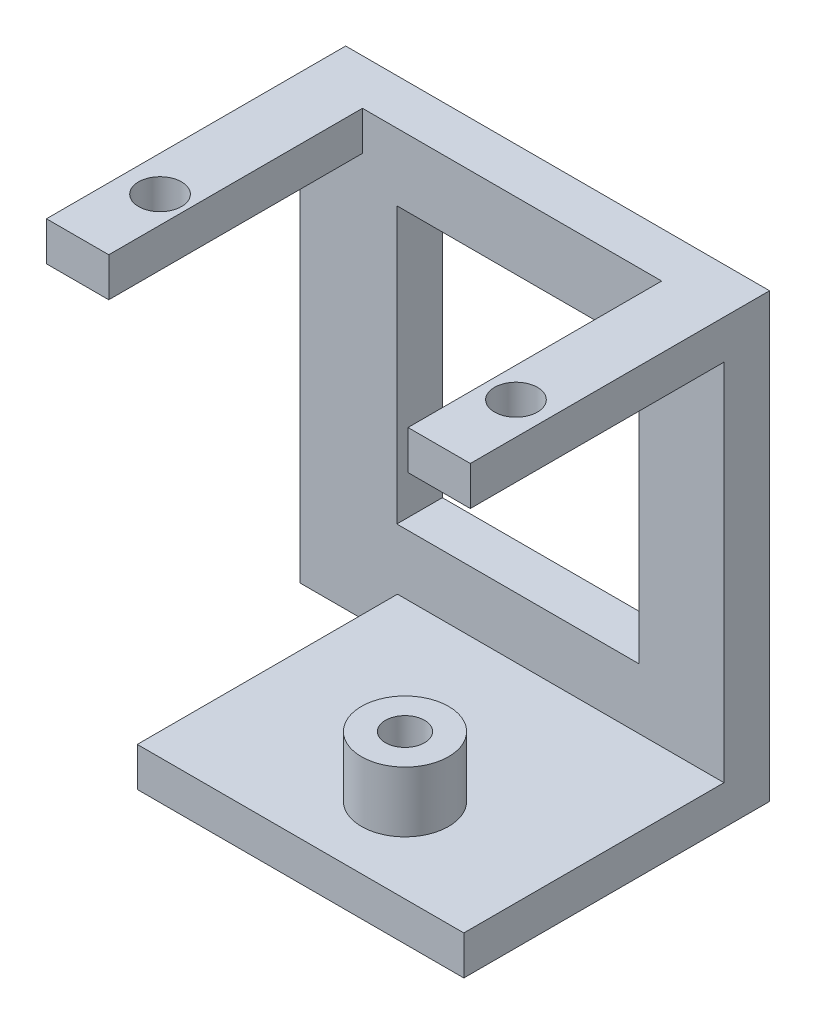
SolidWorks part; units mm, degrees
ref_plane "前视基准面" through (0, 0, 0) normal (0, 0, 1) x (1, 0, 0)
ref_plane "上视基准面" through (0, 0, 0) normal (0, 1, 0) x (1, 0, 0)
ref_plane "右视基准面" through (0, 0, 0) normal (1, 0, 0) x (0, 0, -1)
sketch "草图1" plane through (0, 0, 0) normal (0, 1, 0) x (1, 0, 0)
  line L0 (-0.1205, 5.3451) -> (-0.1205, 14.3596) construction
  line L13 (-16.4112, 17) -> (-11.6205, 17)
  line L14 (-16.4112, 17) -> (-16.4112, -6)
  line L19 (-16.4112, -6) -> (-11.6205, -6)
  line L20 (-11.6205, 17) -> (-11.6205, -6)
  line L21 (-16.4112, 17) -> (-11.6205, -6) construction
  line L22 (-16.4112, -6) -> (-11.6205, 17) construction
  line L23 (11.3795, 17) -> (16.1703, 17)
  line L24 (11.3795, 17) -> (11.3795, -6)
  line L25 (11.3795, -6) -> (16.1703, -6)
  line L26 (16.1703, 17) -> (16.1703, -6)
  line L27 (11.3795, 17) -> (16.1703, -6) construction
  line L28 (11.3795, -6) -> (16.1703, 17) construction
  line L29 (-11.6205, 12.2078) -> (11.3795, 12.2078) construction
  point P4 (-14.0158, 5.5)
  point P9 (13.7749, 5.5)
  point P14 (-0.1205, 12.2078)
  dimension "D1" = 23
  dimension "D2" = 6
  dimension "D3" = 23
extrude "凸台-拉伸1" add sketch "草图1" along normal mid plane 3
sketch "草图2" plane through (0, 0, 0) normal (0, 1, 0) x (1, 0, 0)
  line L0 (-13.68, 0) -> (13.68, 0) construction
  circle A0 centre (-13.68, 0) radius 1.65
  circle A1 centre (13.68, 0) radius 1.65
  point P3 (0, 0)
  dimension "D2" = 3.3
  dimension "D3" = 3.3
  dimension "D1" = 27.36
extrude "切除-拉伸1" cut sketch "草图2" against normal through all both and the other way through all
sketch "草图4" plane through (-11.6205, 0, 0) normal (1, 0, 0) x (0, 0, -1)
  line L0 (-6, -1.5) -> (17, -1.5) construction
  line L1 (17, 1.5) -> (13.5, 1.5)
  line L2 (17, 1.5) -> (17, -1.5)
  line L3 (17, -1.5) -> (13.5, -1.5)
  line L4 (13.5, 1.5) -> (13.5, -1.5)
  line L5 (17, 1.5) -> (13.5, -1.5) construction
  line L6 (17, -1.5) -> (13.5, 1.5) construction
  point P4 (15.25, 0)
  dimension "D1" = 3.5
extrude "凸台-拉伸3" add sketch "草图4" along normal up to next (23 mm away)
sketch "草图3" plane through (-11.6205, 0, 0) normal (1, 0, 0) x (0, 0, -1)
  line L0 (-6, 1.5) -> (17, 1.5) construction
  line L1 (6.5, 1.5) -> (8.5, 1.5)
  line L2 (6.5, 1.5) -> (6.5, -1.5)
  line L3 (6.5, -1.5) -> (8.5, -1.5)
  line L4 (8.5, 1.5) -> (8.5, -1.5)
  line L5 (6.5, 1.5) -> (8.5, -1.5) construction
  line L6 (6.5, -1.5) -> (8.5, 1.5) construction
  line L7 (-6, -1.5) -> (17, -1.5) construction
  line L8 (-6, 1.5) -> (-6, -1.5) construction
  point P4 (7.5, 0)
  dimension "D1" = 12.5
  dimension "D2" = 2
sketch "草图5" plane through (0, -1.5, 0) normal (0, -1, 0) x (-1, 0, 0)
  line L1 (-16.1703, 13.5) -> (16.4112, 13.5)
  line L2 (-16.1703, 13.5) -> (-16.1703, 17)
  line L3 (-16.1703, 17) -> (16.4112, 17)
  line L4 (16.4112, 13.5) -> (16.4112, 17)
  line L5 (-16.1703, 13.5) -> (16.4112, 17) construction
  line L6 (-16.1703, 17) -> (16.4112, 13.5) construction
  line L7 (-11.3795, 13.5) -> (11.6205, 13.5) construction
  line L42 (-16.1703, 17) -> (-16.1703, -6) construction
  point P4 (0.1205, 15.25)
  point P10 (-11.3795, 15.5)
  point P11 (-11.3795, 19)
  point P12 (-11.3795, 19)
  point P13 (-11.3795, 15.5)
  point P14 (-11.3795, 19)
  point P15 (11.6205, 19)
  point P16 (-11.3795, 15.5)
  point P17 (11.6205, 15.5)
  point P18 (-11.3795, 15.5)
  point P19 (11.6205, 15.5)
  point P20 (-11.3795, 19)
  point P21 (11.6205, 19)
  point P22 (11.6205, 19)
  point P23 (11.6205, 15.5)
  point P24 (11.6205, 15.5)
  point P25 (11.6205, 19)
  point P26 (11.6205, 19)
  point P27 (16.4112, 19)
  point P28 (11.6205, -6)
  point P29 (11.6205, 19)
  point P30 (16.4112, -6)
  point P31 (11.6205, -6)
  point P32 (16.4112, 19)
  point P33 (16.4112, -6)
  point P34 (11.6205, 19)
  point P35 (16.4112, 19)
  point P36 (11.6205, -6)
  point P37 (11.6205, 19)
  point P38 (16.4112, -6)
  point P39 (11.6205, -6)
  point P40 (16.4112, 19)
  point P41 (16.4112, -6)
  point P42 (13.68, 0)
  point P43 (15.2579, 0.4824)
  point P44 (13.68, 0)
  point P45 (15.2579, 0.4824)
  point P46 (-11.3795, 19)
  point P47 (-11.3795, -6)
  point P48 (-11.3795, -6)
  point P49 (-16.1703, -6)
  point P50 (-16.1703, -6)
  point P51 (-16.1703, 19)
  point P52 (-16.1703, 19)
  point P53 (-11.3795, 19)
  point P54 (-11.3795, 19)
  point P55 (-11.3795, -6)
  point P56 (-11.3795, -6)
  point P57 (-16.1703, -6)
  point P58 (-16.1703, -6)
  point P59 (-16.1703, 19)
  point P60 (-16.1703, 19)
  point P61 (-11.3795, 19)
  point P62 (-13.68, 0)
  point P63 (-12.1021, 0.4824)
  point P64 (-13.68, 0)
  point P65 (-12.1021, 0.4824)
  point P66 (0.1205, -199992.6549)
  point P67 (0.1205, 200016.3596)
  point P68 (16.4112, 19)
  point P69 (11.6205, 19)
  point P70 (16.4112, 19)
  point P71 (16.4112, -6)
  point P72 (16.4112, -6)
  point P73 (11.6205, -6)
  point P74 (11.6205, 19)
  point P75 (11.6205, -6)
  point P76 (16.4112, 19)
  point P77 (11.6205, -6)
  point P78 (16.4112, -6)
  point P79 (11.6205, 19)
  point P80 (-11.3795, 19)
  point P81 (-16.1703, 19)
  point P82 (-11.3795, 19)
  point P83 (-11.3795, -6)
  point P84 (-11.3795, -6)
  point P85 (-16.1703, -6)
extrude "凸台-拉伸4" add sketch "草图5" along normal blind 31
sketch "草图6" plane through (0, 0, -13.5) normal (0, 0, 1) x (1, 0, 0)
  line L0 (-16.4112, -32.5) -> (-16.4112, -1.5) construction
  line L1 (-16.4112, -29.5) -> (16.1703, -29.5)
  line L2 (-16.4112, -29.5) -> (-16.4112, -32.5)
  line L3 (-16.4112, -32.5) -> (16.1703, -32.5)
  line L4 (16.1703, -29.5) -> (16.1703, -32.5)
  line L5 (-16.4112, -29.5) -> (16.1703, -32.5) construction
  line L6 (-16.4112, -32.5) -> (16.1703, -29.5) construction
  point P4 (-0.1205, -31)
  dimension "D1" = 3
extrude "凸台-拉伸5" add sketch "草图6" along normal blind 20
sketch "草图7" plane through (0, -29.5, 0) normal (0, 1, 0) x (1, 0, 0)
  line L0 (-13.68, 0) -> (13.68, 0) construction
  point P0 (0, 0)
  point P1 (5.15, 0)
  point P6 (0, 0)
  dimension "D1" = 27.36
  dimension "D2" = 8.53
sketch "草图8" plane through (0, -29.5, 0) normal (0, 1, 0) x (1, 0, 0)
  circle A0 centre (5.15, 0) radius 3.35
  dimension "D1" = 6.7
extrude "凸台-拉伸6" add sketch "草图8" along normal blind 6
sketch "草图9" plane through (0, -23.5, 0) normal (0, 1, 0) x (1, 0, 0)
  circle A0 centre (5.15, 0) radius 1.5
  dimension "D1" = 3
extrude "切除-拉伸2" cut sketch "草图9" against normal up to next
sketch "草图10" plane through (0, 0, -17) normal (0, 0, -1) x (-1, 0, 0)
  line L1 (-9.6277, -3.6672) -> (8.9791, -3.6672)
  line L2 (-9.6277, -3.6672) -> (-9.6277, -24.8524)
  line L3 (-9.6277, -24.8524) -> (8.9791, -24.8524)
  line L4 (8.9791, -3.6672) -> (8.9791, -24.8524)
  line L5 (-9.6277, -3.6672) -> (8.9791, -24.8524) construction
  line L6 (-9.6277, -24.8524) -> (8.9791, -3.6672) construction
  point P4 (-0.3243, -14.2598)
extrude "切除-拉伸3" cut sketch "草图10" against normal through all
sketch "草图11" plane through (0, -29.5, 0) normal (0, 1, 0) x (1, 0, 0)
  line L0 (16.1703, -6.5) -> (-16.4112, -6.5) construction
  line L5 (-16.4112, 13.5) -> (-8.9302, 13.5)
  line L6 (-16.4112, 13.5) -> (-16.4112, -6.5)
  line L7 (-16.4112, -6.5) -> (-8.9302, -6.5)
  line L8 (-8.9302, 13.5) -> (-8.9302, -6.5)
  line L9 (-16.4112, 13.5) -> (-8.9302, -6.5) construction
  line L10 (-16.4112, -6.5) -> (-8.9302, 13.5) construction
  point P4 (-12.6707, 3.5)
extrude "切除-拉伸4" cut sketch "草图11" against normal blind 10
